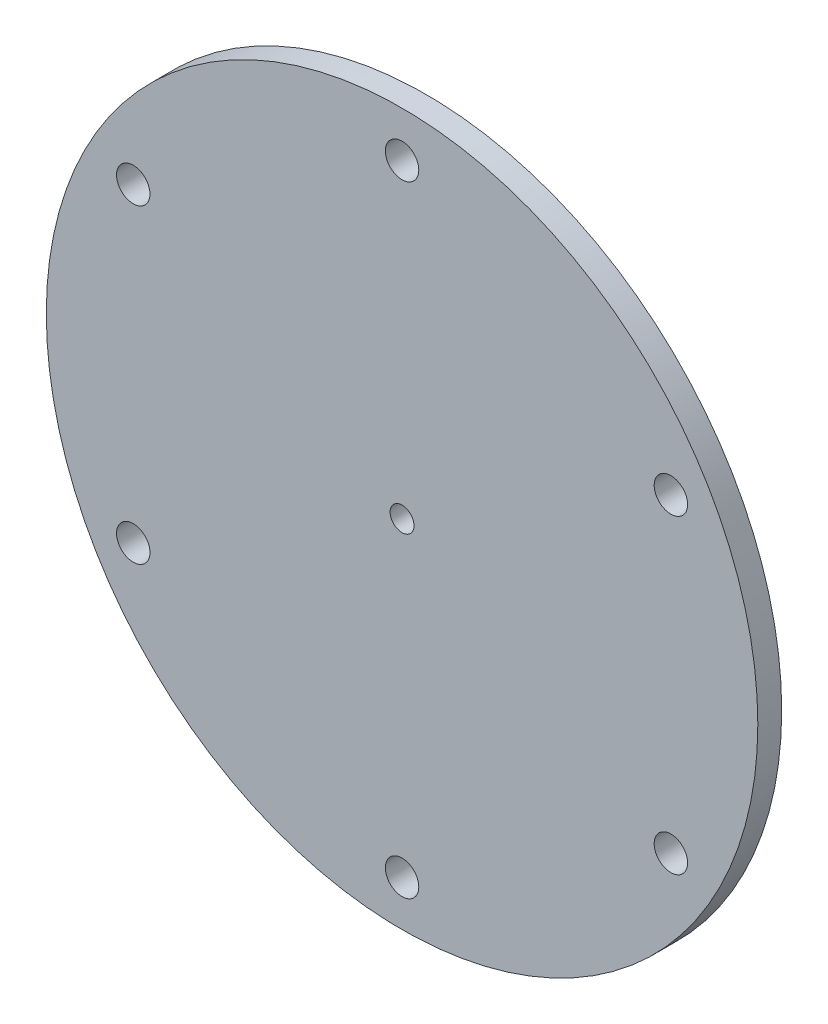
SolidWorks part; units mm, degrees
ref_plane "Спереди" through (0, 0, 0) normal (0, 0, 1) x (1, 0, 0)
ref_plane "Сверху" through (0, 0, 0) normal (0, 1, 0) x (1, 0, 0)
ref_plane "Справа" through (0, 0, 0) normal (1, 0, 0) x (0, 0, -1)
sketch "Эскиз1" plane through (0, 0, 0) normal (0, 0, 1) x (1, 0, 0)
  circle A0 centre (0, 0) radius 44.7
  circle A1 centre (0, 0) radius 1.5
  circle A2 centre (0, 39) radius 2.1
  dimension "D1" = 89.4
  dimension "D2" = 3
  dimension "D3" = 4.2
  dimension "D4" = 39
extrude "Бобышка-Вытянуть1" add sketch "Эскиз1" along normal blind 3 contours A0
extrude "Вырез-Вытянуть1" cut sketch "Эскиз1<5>" along normal blind 73.5 contours A1
sketch "Эскиз1<5>" plane through (0, 0, 0) normal (0, 0, 1) x (1, 0, 0) same geometry as "Эскиз1"
extrude "Вырез-Вытянуть2" cut sketch "Эскиз1<6>" along normal blind 42 contours A2
sketch "Эскиз1<6>" plane through (0, 0, 0) normal (0, 0, 1) x (1, 0, 0) same geometry as "Эскиз1"
pattern_circular "Круговой массив1" count 6 over 360 about axis through (0, 0, 3) along (0, 0, -1) of "Вырез-Вытянуть2"
